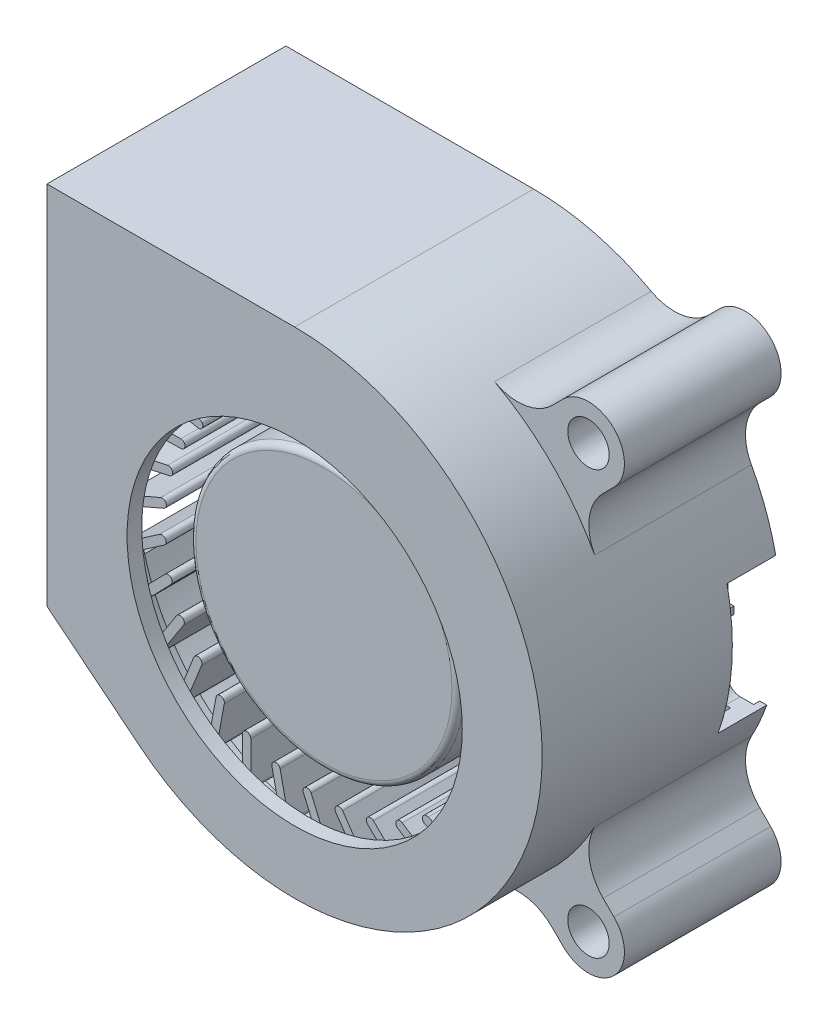
SolidWorks part; units mm, degrees
ref_plane "Спереди" through (0, 0, 0) normal (0, 0, 1) x (1, 0, 0)
ref_plane "Сверху" through (0, 0, 0) normal (0, 1, 0) x (1, 0, 0)
ref_plane "Справа" through (0, 0, 0) normal (1, 0, 0) x (0, 0, -1)
sketch "Эскиз1" plane through (0, 0, 0) normal (0, 0, 1) x (1, 0, 0)
  line L0 (-20.3193, 21.7023) -> (-20.3193, -8.2977)
  line L1 (-20.3193, -8.2977) -> (-12.7335, -14.4075)
  line L2 (-20.3193, 21.7023) -> (0, 21.7023)
  line L3 (0, 1.4023) -> (20.3, 21.7023) construction
  line L4 (20.3, 21.7023) -> (20.3, -18.8977) construction
  line L5 (20.3, -18.8977) -> (0, 1.4023) construction
  line L6 (20.3, -18.8977) -> (-20.3, -18.8977) construction
  line L7 (-20.3, -18.8977) -> (0, 1.4023) construction
  line L8 (-19.436, -13.8618) -> (-16.7482, -11.174)
  line L9 (-15.264, -18.0337) -> (-12.1159, -14.8856)
  line L10 (17.35, -18.8977) -> (0, -18.8977)
  line L11 (12.1159, -14.8856) -> (15.264, -18.0337)
  line L12 (19.436, -13.8618) -> (16.2879, -10.7137)
  line L13 (15.264, 20.8382) -> (12.1159, 17.6901)
  line L14 (19.436, 16.6663) -> (16.2879, 13.5182)
  line L15 (-20.3193, 20.5023) -> (0.1052, 20.502)
  line L16 (-17.6473, -5.904) -> (-20.3193, -7.0102)
  circle A0 centre (0, 0) radius 13.7477
  arc A1 (-12.7335, -14.4075) -> (0, 21.7023) centre (0, 1.4023) ccw
  circle A2 centre (17.35, 18.7523) radius 1.7
  circle A3 centre (-17.35, -15.9477) radius 1.7
  circle A4 centre (17.35, -15.9477) radius 1.7
  arc A5 (-19.436, -13.8618) -> (-15.264, -18.0337) centre (-17.35, -15.9477) ccw
  arc A6 (15.264, -18.0337) -> (19.436, -13.8618) centre (17.35, -15.9477) ccw
  arc A7 (19.436, 16.6663) -> (15.264, 20.8382) centre (17.35, 18.7523) ccw
  arc A8 (-17.6473, -5.904) -> (0.1052, 20.502) centre (0, 1.4023) ccw
  dimension "D1" = 30
  dimension "D2" = 20.3
  dimension "D3" = 27.4955
  dimension "D4" = 3.4
  dimension "D5" = 5.9
  dimension "D8" = 19.1
  dimension "D6" = 20.3193
  dimension "D7" = 1.4023
extrude "Бобышка-Вытянуть1" add sketch "Эскиз1" along normal blind 12.85 contours L14 A7 L13 A1 A2 | L11 A6 L12 A1 A4 | L8 A5 L9 A1 L1 A3 region at (13.7718, 19.1823, 0) region at (-14.8114, -12.8784, 0) region at (17.7801, -12.3696, 0)
extrude "Бобышка-Вытянуть2" add sketch "Эскиз1<4>" along normal blind 1.7 separate body contours L16 A8 L15 L0 A0 | A0 region at (-10.107, 19.9532, 0) region at (0, 0, 0)
sketch "Эскиз1<4>" plane through (0, 0, 0) normal (0, 0, 1) x (1, 0, 0) same geometry as "Эскиз1"
extrude "Бобышка-Вытянуть3" add sketch "Эскиз1<5>" along normal blind 19.6 contours A8 L16 L0 L1 A1 L2 L15 region at (-10.1596, 21.128, 0)
sketch "Эскиз1<5>" plane through (0, 0, 0) normal (0, 0, 1) x (1, 0, 0) same geometry as "Эскиз1"
extrude "Бобышка-Вытянуть4" add sketch "Эскиз1<6>" against normal blind 1.2 from vertex contours L16 A8 L15 L0 A0 region at (-10.107, 19.9532, 0) starting at point (-20.3193, 20.5023, 19.6)
sketch "Эскиз1<6>" plane through (0, 0, 0) normal (0, 0, 1) x (1, 0, 0) same geometry as "Эскиз1"
sketch "Эскиз2" plane through (0, 0, 0) normal (0, 0, -1) x (-1, 0, 0)
  line L8 (-10.3957, -0.3) -> (-19.6807, -0.3)
  line L9 (-0.3, 10.3957) -> (-0.2869, 21.1544)
  line L10 (10.3957, 0.3) -> (19.8766, 0.3)
  line L11 (0.3, -10.3957) -> (0.301, -18.3496)
  line L12 (19.887, -8.0245) -> (12.3908, -13.9826)
  line L13 (19.8505, 21.1544) -> (19.8766, 0.3)
  line L14 (19.8505, 21.1544) -> (0.3001, 21.1544)
  line L15 (-10.3957, 0.3) -> (-19.7234, 0.3)
  line L16 (0.3, 10.3957) -> (0.3001, 21.1544)
  line L17 (10.3957, -0.3) -> (19.8773, -0.3)
  line L18 (-0.3, -10.3957) -> (-0.301, -18.3496)
  line L19 (19.8773, -0.3) -> (19.887, -8.0245)
  arc A0 (0.301, -18.3496) -> (12.3908, -13.9826) centre (0, 1.4023) ccw
  arc A1 (10.3957, 0.3) -> (0.3, 10.3957) centre (0, 0) ccw
  arc A2 (0, 21.7023) -> (-12.1159, 17.6901) centre (0, 1.4023) ccw construction
  arc A5 (-0.2869, 21.1544) -> (-19.7234, 0.3) centre (0, 1.4023) ccw
  circle A6 centre (0, 0) radius 9.8
  arc A8 (-0.3, 10.3957) -> (-10.3957, 0.3) centre (0, 0) ccw
  arc A12 (-19.6807, -0.3) -> (-0.301, -18.3496) centre (0, 1.4023) ccw
  arc A13 (-10.3957, -0.3) -> (-0.3, -10.3957) centre (0, 0) ccw
  arc A14 (0.3, -10.3957) -> (10.3957, -0.3) centre (0, 0) ccw
extrude "Вырез-Вытянуть1" cut sketch "Эскиз2" against normal blind 0.5
sketch "Эскиз3" plane through (0, 0, 0) normal (0, 0, -1) x (-1, 0, 0)
  line L1 (-25.6875, -5.3927) -> (-16.4308, -5.3927)
  line L2 (-25.6875, -5.3927) -> (-25.6875, 5.6073)
  line L3 (-25.6875, 5.6073) -> (-16.4308, 5.6073)
  line L4 (-16.4308, -5.3927) -> (-16.4308, 5.6073)
  line L5 (-25.6875, -5.3927) -> (-16.4308, 5.6073) construction
  line L6 (-25.6875, 5.6073) -> (-16.4308, -5.3927) construction
extrude "Вырез-Вытянуть2" cut sketch "Эскиз3" against normal blind 4
sketch "Эскиз4" plane through (0, 0, 0) normal (0, 0, -1) x (-1, 0, 0)
  line L0 (1.85, -12.5557) -> (3.7573, -12.5557)
  line L2 (-3.7736, -9.046) -> (-3.7736, -12.5557)
  line L3 (-3.7736, -12.5557) -> (-1.85, -12.5557)
  line L4 (3.7573, -9.0528) -> (3.7573, -12.5557)
  line L5 (-0.0082, -9.8) -> (3.7573, -12.5557) construction
  line L6 (-3.7736, -12.5557) -> (-0.0082, -9.8) construction
  line L7 (-1.85, -18.9877) -> (1.85, -18.9877)
  line L8 (-1.85, -18.9877) -> (-1.85, -12.5557)
  line L10 (1.85, -18.9877) -> (1.85, -12.5557)
  line L11 (-1.85, -18.9877) -> (0, -14.4877) construction
  line L12 (0, -14.4877) -> (1.85, -18.9877) construction
  circle A0 centre (0, 0) radius 9.8 construction
  arc A1 (-3.7736, -9.046) -> (3.7573, -9.0528) centre (0, 0) ccw
  point P0 (-0.0082, -9.8)
  point P7 (0, -14.4877)
extrude "Вырез-Вытянуть3" cut sketch "Эскиз4" against normal blind 2
sketch "Эскиз5" plane through (0, -12.5557, 0) normal (0, 1, 0) x (1, 0, 0)
  line L0 (1.85, -1.7) -> (1.85, -2)
  line L1 (1.85, -2) -> (-1.85, -2)
  line L2 (-1.85, -2) -> (-1.85, -1.7)
  line L3 (2.8118, -1.7) -> (2.8118, -3.2)
  line L4 (1.85, -1.7) -> (3.7736, -1.7) construction
  line L5 (2.8118, -3.2) -> (-2.8036, -3.2)
  line L6 (-2.8036, -3.2) -> (-2.8036, -1.7)
  line L7 (-3.7573, -1.7) -> (-1.85, -1.7) construction
  line L8 (2.8118, -1.7) -> (1.85, -1.7)
  line L9 (-1.85, -1.7) -> (-2.8036, -1.7)
  dimension "D1" = 1.2
extrude "Бобышка-Вытянуть5" add sketch "Эскиз5" against normal up to next
fillet "Скругление1" radius 4 6 edges at (16.2879, 13.5182, 6.425) (12.1159, 17.6901, 6.425) (-12.1159, -14.8856, 6.425) (-16.7482, -11.174, 6.425) (16.2879, -10.7137, 6.425) (12.1159, -14.8856, 6.425)
fillet "Скругление2" radius 1 14 edges at (10.3957, -0.3, 0.25) (10.3957, 0.3, 0.25) (-19.887, -8.0245, 0.25) (-19.8773, -0.3, 0.25) (-10.3957, -0.3, 0.25) (-10.3957, 0.3, 0.25) (-19.8766, 0.3, 0.25) (-19.8505, 21.1544, 0.25) (-0.3001, 21.1544, 0.25) (0.2869, 21.1544, 0.25) (0.3, 10.3957, 0.25) (-0.3, 10.3957, 0.25) (16.4308, -5.3927, 1.1) (16.4308, 5.6073, 1.1)
ref_plane "Плоскость1" through (0, 0, 4.2) normal (0, 0, 1) x (1, 0, 0)
sketch "Эскиз6" plane through (0, 0, 4.2) normal (0, 0, 1) x (1, 0, 0)
  line L0 (-16.4475, 0) -> (-13.272, 1.3682) construction
  line L1 (-16.5836, 0.3159) -> (-13.4081, 1.6841)
  line L2 (-16.3114, -0.3159) -> (-13.1359, 1.0522)
  circle A0 centre (0, 0) radius 16.7732
  circle A1 centre (0, 0) radius 16.4475
  circle A2 centre (0, 0) radius 11
  arc A3 (-16.5836, 0.3159) -> (-16.3114, -0.3159) centre (-16.4475, 0) ccw
  arc A4 (-13.1359, 1.0522) -> (-13.4081, 1.6841) centre (-13.272, 1.3682) ccw
  point P7 (-14.8598, 0.6841)
extrude "Бобышка-Вытянуть6" add sketch "Эскиз6" along normal blind 1.2 separate body contours A4 L2 A3 A1 L1 A2 | L2 A4 L1 A1 A3 region at (0.1829, 15.9813, 4.2) region at (-14.7325, 0.7341, 4.2)
extrude "Бобышка-Вытянуть7" add sketch "Эскиз6<3>" along normal blind 13 contours L2 A4 L1 A1 A3 region at (-14.7325, 0.7341, 4.2)
sketch "Эскиз6<3>" plane through (0, 0, 4.2) normal (0, 0, 1) x (1, 0, 0) same geometry as "Эскиз6"
pattern_circular "Круговой массив6" count 32 over 360 about axis through (0, 0, 5.4) along (0, 0, -1) of "Бобышка-Вытянуть7"
extrude "Бобышка-Вытянуть8" add sketch "Эскиз6<4>" against normal blind 1.2 from offset 13 contours A3 L1 A1 A0 | L1 A3 A0 A1 region at (-16.7346, 0.2661, 4.2) region at (-16.5891, 0.0029, 4.2)
sketch "Эскиз6<4>" plane through (0, 0, 4.2) normal (0, 0, 1) x (1, 0, 0) same geometry as "Эскиз6"
extrude "Бобышка-Вытянуть9" add sketch "Эскиз6<5>" along normal blind 13 contours A2 region at (0, 0, 4.2)
sketch "Эскиз6<5>" plane through (0, 0, 4.2) normal (0, 0, 1) x (1, 0, 0) same geometry as "Эскиз6"
fillet "Скругление3" radius 0.5 1 edges at (11, 0, 17.2)
